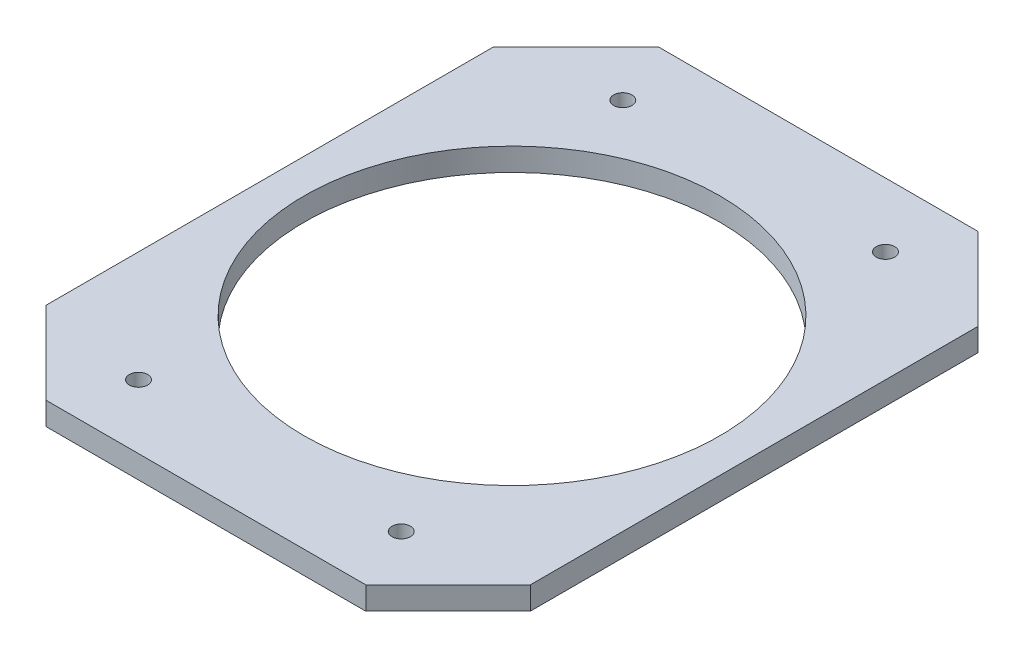
SolidWorks part; units mm, degrees
material "6061-T6 (SS)"
ref_plane "Front Plane" through (0, 0, 0) normal (0, 0, 1) x (1, 0, 0)
ref_plane "Top Plane" through (0, 0, 0) normal (0, 1, 0) x (1, 0, 0)
ref_plane "Right Plane" through (0, 0, 0) normal (1, 0, 0) x (0, 0, -1)
sketch "Sketch1" plane through (0, 0, 0) normal (0, 1, 0) x (1, 0, 0)
  line L0 (-67.31, 62.23) -> (-44.45, 85.09)
  line L1 (-44.45, -85.09) -> (44.45, -85.09)
  line L2 (-67.31, -62.23) -> (-67.31, 62.23)
  line L3 (-44.45, 85.09) -> (44.45, 85.09)
  line L4 (67.31, -62.23) -> (67.31, 62.23)
  line L5 (-85.725, -85.725) -> (85.725, 85.725) construction
  line L6 (-85.725, 85.725) -> (85.725, -85.725) construction
  line L7 (44.45, 85.09) -> (67.31, 62.23)
  line L8 (67.31, -62.23) -> (44.45, -85.09)
  line L9 (-67.31, -62.23) -> (-44.45, -85.09)
  circle A0 centre (0, 0) radius 54.61 construction
  point P0 (0, 0)
  point P16 (-67.31, 0)
  point P18 (0, 85.09)
  dimension "D4" = 109.22
  dimension "D1" = 171.45
  dimension "D2" = 171.45
  dimension "D3" = 88.9
  dimension "D5" = 170.18
  dimension "D6" = 12.7
extrude "Boss-Extrude1" add sketch "Sketch1" along normal blind 6.35
hole_wizard "#10 Clearance Hole1" positions "Sketch3" profile "Sketch2" hole size "#10" standard "ANSI Inch" end condition through all
sketch "Sketch3" plane through (0, 6.35, 0) normal (0, 1, 0) x (-1, 0, 0)
  line L0 (-36.5125, -67.31) -> (0, 0) construction
  line L1 (0, 0) -> (36.5125, -67.31) construction
  line L5 (-1114.9397, -57.15) -> (48885.0603, -57.15) construction
  point P0 (36.5125, -67.31)
  point P1 (-36.5125, -67.31)
  dimension "D1" = 73.025
  dimension "D3" = 57.15
  dimension "D4" = 10.16
sketch "Sketch2" plane through (-36.5125, 6.35, -67.31) normal (1, 0, 0) x (0, 0, 1)
  line L0 (0, 0) -> (0, 6.35)
  line L1 (0, 6.35) -> (2.5527, 6.35)
  line L2 (2.5527, 6.35) -> (2.5527, 0)
  line L5 (2.5527, 0) -> (0, 0)
  line L11 (0, -6.35) -> (0, 107.95) construction
  dimension "Thru Hole Dia." = 5.1054
  dimension "Thru Hole Depth" = 6.35
ref_axis "Axis1" through (0, 0, 0) along (0, 1, 0)
pattern_circular "CirPattern1" count 2 over 360 about axis through (0, 0, 0) along (0, 1, 0) of "#10 Clearance Hole1"
sketch "Sketch4" plane through (0, 6.35, 0) normal (0, 1, 0) x (1, 0, 0)
  circle A0 centre (0, 0) radius 57.785
  dimension "D1" = 115.57
extrude "Cut-Extrude1" cut sketch "Sketch4" against normal through all
